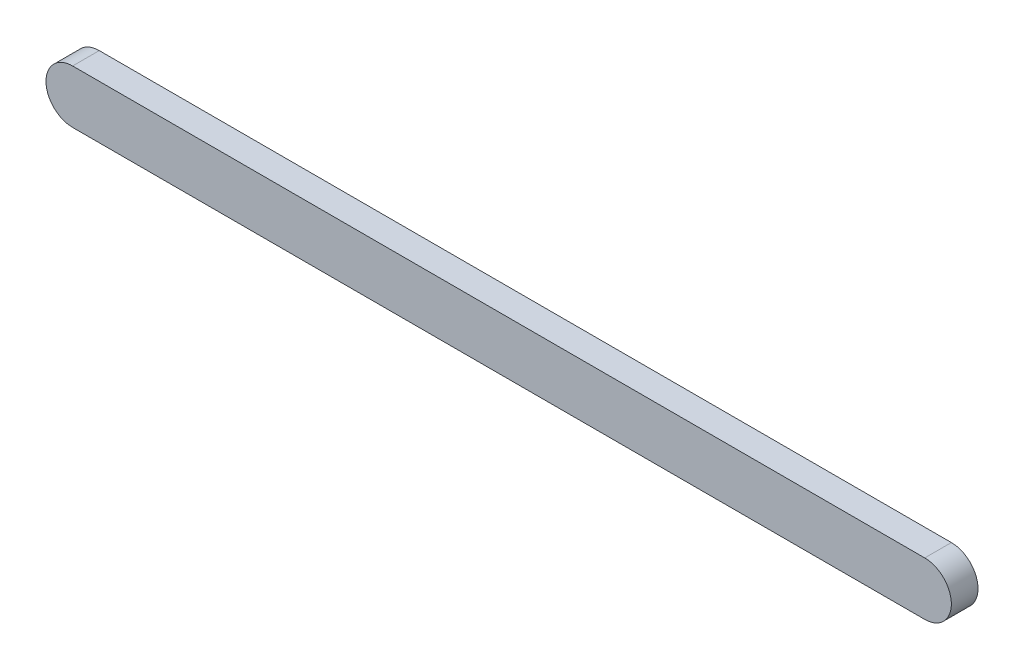
SolidWorks part; units mm, degrees
ref_plane "Front Plane" through (0, 0, 0) normal (0, 0, 1) x (1, 0, 0)
ref_plane "Top Plane" through (0, 0, 0) normal (0, 1, 0) x (1, 0, 0)
ref_plane "Right Plane" through (0, 0, 0) normal (1, 0, 0) x (0, 0, -1)
sketch "Sketch1" plane through (0, 0, 0) normal (0, 0, 1) x (1, 0, 0)
  line L0 (-53.3333, -2.6667) -> (26.6667, -2.6667) construction
  line L1 (-53.3333, -0.1667) -> (26.6667, -0.1667)
  line L2 (-53.3333, -5.1667) -> (26.6667, -5.1667)
  arc A0 (-53.3333, -0.1667) -> (-53.3333, -5.1667) centre (-53.3333, -2.6667) ccw
  arc A1 (26.6667, -5.1667) -> (26.6667, -0.1667) centre (26.6667, -2.6667) ccw
  point P2 (-13.3333, -2.6667)
  dimension "D1" = 2.5
  dimension "D2" = 80
extrude "Boss-Extrude1" add sketch "Sketch1" along normal blind 2.5
ref_axis "Axis1" through (26.6667, -2.6667, 0) along (0, 0, 1)
ref_axis "Axis2" through (-53.3333, -2.6667, 0) along (0, 0, 1)
